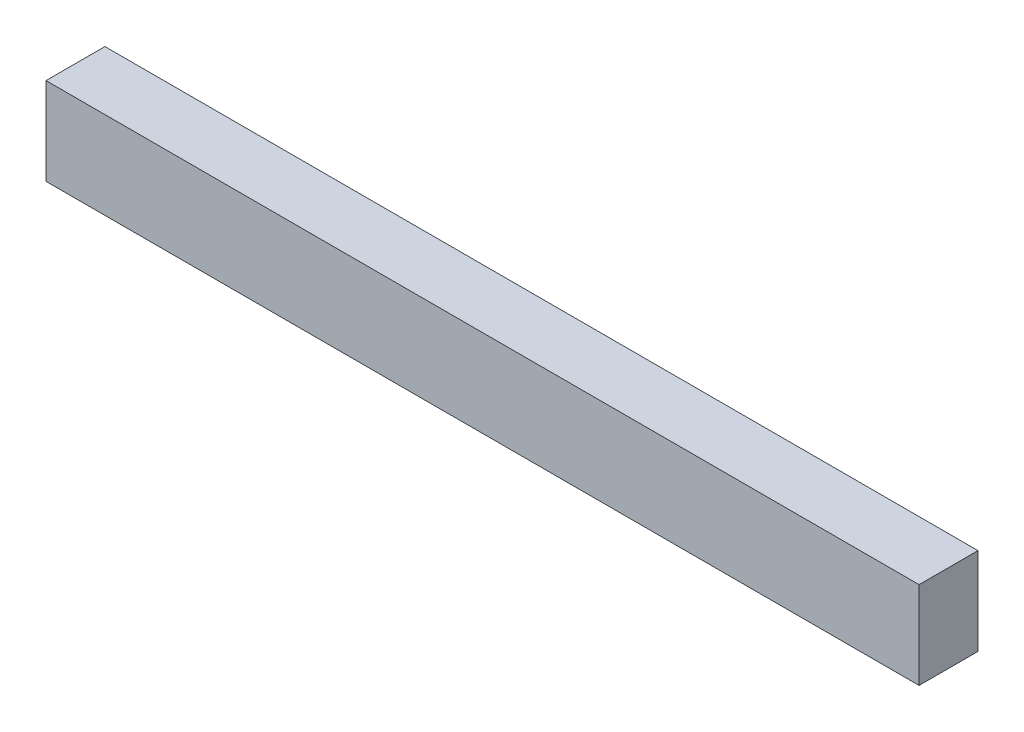
SolidWorks part; units mm, degrees
ref_plane "Plan de face" through (0, 0, 0) normal (0, 0, 1) x (1, 0, 0)
ref_plane "Plan de dessus" through (0, 0, 0) normal (0, 1, 0) x (1, 0, 0)
ref_plane "Plan de droite" through (0, 0, 0) normal (1, 0, 0) x (0, 0, -1)
sketch "Esquisse1" plane through (0, 0, 0) normal (0, 0, 1) x (1, 0, 0)
  line L1 (0, 0) -> (400, 0)
  line L2 (0, 0) -> (0, 40)
  line L3 (0, 40) -> (400, 40)
  line L4 (400, 0) -> (400, 40)
  dimension "D1" = 40
  dimension "D2" = 400
extrude "Boss.-Extru.1" add sketch "Esquisse1" along normal blind 27
